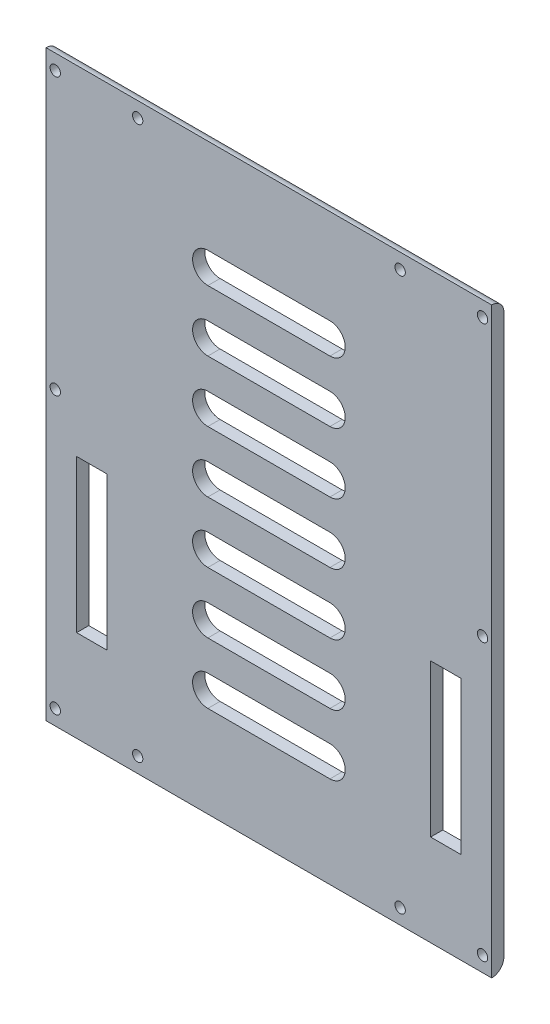
SolidWorks part; units mm, degrees
ref_plane "Front Plane" through (0, 0, 0) normal (1, 0, 0) x (0, 1, 0)
ref_plane "Top Plane" through (0, 0, 0) normal (0, 0, 1) x (0, 1, 0)
ref_plane "Right Plane" through (0, 0, 0) normal (0, 1, 0) x (-1, 0, 0)
sketch "Sketch1" plane through (0, 0, 0) normal (0, 0, 1) x (0, 1, 0)
  line L0 (95.5, 146) -> (95.5, 0) construction
  line L1 (0, 0) -> (191, 0)
  line L2 (0, 0) -> (0, 146)
  line L3 (0, 146) -> (191, 146)
  line L4 (191, 0) -> (191, 146)
  line L5 (35, 93) -> (35, 53) construction
  line L6 (30, 136) -> (80, 136)
  line L7 (30, 136) -> (30, 126)
  line L8 (30, 126) -> (80, 126)
  line L9 (80, 136) -> (80, 126)
  line L10 (30, 20) -> (80, 20)
  line L11 (30, 20) -> (30, 10)
  line L12 (30, 10) -> (80, 10)
  line L13 (80, 20) -> (80, 10)
  line L14 (40, 93) -> (40, 53)
  line L15 (30, 93) -> (30, 53)
  line L16 (0, 73) -> (191, 73) construction
  line L17 (55, 93) -> (55, 53) construction
  line L18 (60, 93) -> (60, 53)
  line L19 (50, 93) -> (50, 53)
  line L20 (75, 93) -> (75, 53) construction
  line L21 (80, 93) -> (80, 53)
  line L22 (70, 93) -> (70, 53)
  line L23 (95, 93) -> (95, 53) construction
  line L24 (100, 93) -> (100, 53)
  line L25 (90, 93) -> (90, 53)
  line L26 (115, 93) -> (115, 53) construction
  line L27 (120, 93) -> (120, 53)
  line L28 (110, 93) -> (110, 53)
  line L29 (135, 93) -> (135, 53) construction
  line L30 (140, 93) -> (140, 53)
  line L31 (130, 93) -> (130, 53)
  line L32 (155, 93) -> (155, 53) construction
  line L33 (160, 93) -> (160, 53)
  line L34 (150, 93) -> (150, 53)
  circle A0 centre (5, 3) radius 1.7
  circle A1 centre (5, 143) radius 1.7
  circle A2 centre (186, 143) radius 1.7
  circle A3 centre (186, 3) radius 1.7
  circle A4 centre (95.5, 143) radius 1.7
  circle A5 centre (95.5, 3) radius 1.7
  arc A6 (40, 93) -> (30, 93) centre (35, 93) ccw
  arc A7 (30, 53) -> (40, 53) centre (35, 53) ccw
  arc A8 (60, 93) -> (50, 93) centre (55, 93) ccw
  arc A9 (50, 53) -> (60, 53) centre (55, 53) ccw
  arc A10 (80, 93) -> (70, 93) centre (75, 93) ccw
  arc A11 (70, 53) -> (80, 53) centre (75, 53) ccw
  arc A12 (100, 93) -> (90, 93) centre (95, 93) ccw
  arc A13 (90, 53) -> (100, 53) centre (95, 53) ccw
  arc A14 (120, 93) -> (110, 93) centre (115, 93) ccw
  arc A15 (110, 53) -> (120, 53) centre (115, 53) ccw
  arc A16 (140, 93) -> (130, 93) centre (135, 93) ccw
  arc A17 (130, 53) -> (140, 53) centre (135, 53) ccw
  arc A18 (160, 93) -> (150, 93) centre (155, 93) ccw
  arc A19 (150, 53) -> (160, 53) centre (155, 53) ccw
  circle A20 centre (5, 30) radius 1.7
  circle A21 centre (186, 30) radius 1.7
  circle A22 centre (186, 116) radius 1.7
  circle A23 centre (5, 116) radius 1.7
  point P29 (35, 73)
  point P37 (0, 73)
  point P41 (55, 73)
  point P48 (75, 73)
  point P55 (95, 73)
  point P62 (115, 73)
  point P69 (135, 73)
  point P76 (155, 73)
  dimension "D7" = 3.4
  dimension "D1" = 191
  dimension "D2" = 146
  dimension "D3" = 3
  dimension "D4" = 5
  dimension "D5" = 3
  dimension "D6" = 5
  dimension "D8" = 30
  dimension "D9" = 10
  dimension "D10" = 10
  dimension "D11" = 10
  dimension "D12" = 50
  dimension "D13" = 10
  dimension "D14" = 40
  dimension "D16" = 10
  dimension "D17" = 10
  dimension "D15" = 7
extrude "Boss-Extrude2" add sketch "Sketch1" along normal blind 4
fillet "Fillet1" radius 4 2 edges at (-73, 191, 0) (-73, 0, 0)
equation "\"MotorDriverLength\"= 60mm"
equation "\"MotorLength\"= 60"
equation "\"MotorDriverWidth\"=45"
equation "\"MotorWidth\"= 37"
equation "\"InnerWallThickness\"=3"
equation "\"BatteryWidth\"= 60"
equation "\"OuterWallThickness\" = 6"
equation "\"CompartmentHeight\"=37"
equation "\"CompartmentWidth\"= \"MotorDriverLength\""
equation "\"MotorDiameter\"=37"
equation "\"BatteryHeight\"=24.2019"
equation "\"MotorDriverHeight\"=20"
equation "\"CircuitHeight\"=30"
equation "\"FanThickness\"= 10"
equation "\"FanHeight\"=50"
equation "\"MotorShaftHole\"=12"
equation "\"BearingBore\"=4"
equation "\"MinShinWidth\"= 20"
equation "\"ShinThickness\"=10"
equation "\"PivotDistance\"=40"
equation "\"ThighLength\"= 200"
equation "\"KneeLength\" =20"
equation "\"HipBore\"=27"
equation "\"ThighThickness\"=20"
equation "\"MaxBending\"=135"
equation "\"MaxStretchingAngle\"= 140"
equation "\"ThighJointDistance\"=157.485"
equation "\"ShinLength\"=100"
equation "\"BearingDiameter\"= 10"
equation "\"CircuitLength\"=50"
equation "\"ChessisInnerWidth\"= \"OuterWallThickness\" * 2 + \"MotorDriverLength\" * 2 + \"InnerWallThickness\" * 3 + \"CircuitLength\""
equation "\"D1@Sketch1\"=\"ChessisInnerWidth\""
equation "\"D2@Sketch1\"=\"MotorLength\"*2 + 20 +\"InnerWallThickness\"*2"
